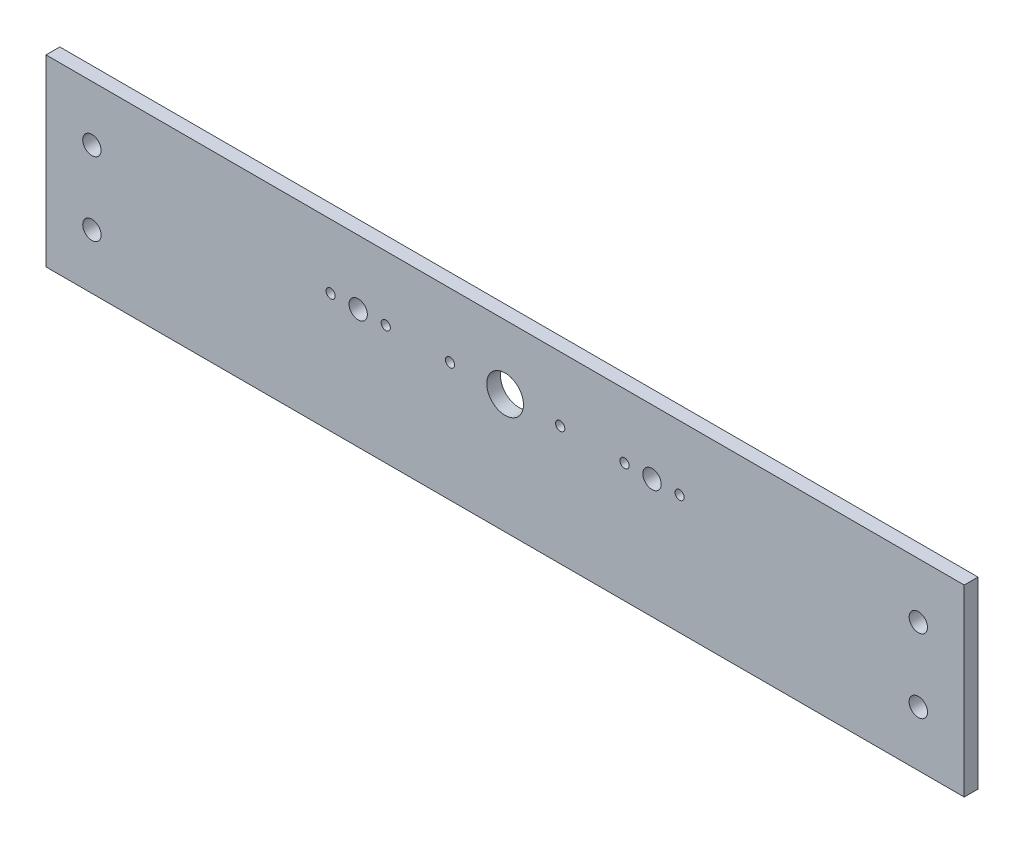
SolidWorks part; units mm, degrees
ref_plane "Front Plane" through (0, 0, 0) normal (0, 0, 1) x (1, 0, 0)
ref_plane "Top Plane" through (0, 0, 0) normal (0, 1, 0) x (1, 0, 0)
ref_plane "Right Plane" through (0, 0, 0) normal (1, 0, 0) x (0, 0, -1)
sketch "Sketch2" plane through (0, 0, 0) normal (0, 0, 1) x (1, 0, 0)
  line L1 (0, 100) -> (500, 100)
  line L2 (0, 100) -> (0, 0)
  line L3 (0, 0) -> (500, 0)
  line L4 (500, 100) -> (500, 0)
  dimension "D1" = 100
  dimension "D2" = 500
extrude "Boss-Extrude1" add sketch "Sketch2" along normal blind 7.5
sketch "Sketch9" plane through (0, 0, 7.5) normal (0, 0, 1) x (1, 0, 0)
  line L0 (500, 100) -> (0, 100) construction
  circle A0 centre (170, 65) radius 5
  circle A1 centre (185, 65) radius 2.5
  circle A2 centre (155, 65) radius 2.5
  circle A3 centre (330, 65) radius 5
  circle A4 centre (345, 65) radius 2.5
  circle A5 centre (315, 65) radius 2.5
  circle A6 centre (250, 65) radius 10
  circle A7 centre (280, 65) radius 2.5
  circle A8 centre (220, 65) radius 2.5
  dimension "D1" = 35
extrude "Cut-Extrude3" cut sketch "Sketch9" against normal through all
sketch "Sketch11" plane through (0, 0, 7.5) normal (0, 0, 1) x (1, 0, 0)
  line L0 (500, 100) -> (0, 100) construction
  line L1 (0, 0) -> (500, 0) construction
  line L2 (0, 100) -> (0, 0) construction
  line L3 (500, 0) -> (500, 100) construction
  circle A0 centre (25, 70) radius 5
  circle A1 centre (25, 30) radius 5
  circle A2 centre (475, 30) radius 5
  circle A3 centre (475, 70) radius 5
  dimension "D1" = 40
  dimension "D3" = 30
  dimension "D2" = 40
  dimension "D4" = 30
  dimension "D5" = 30
  dimension "D6" = 30
  dimension "D7" = 25
  dimension "D8" = 25
extrude "Cut-Extrude4" cut sketch "Sketch11" against normal through all
